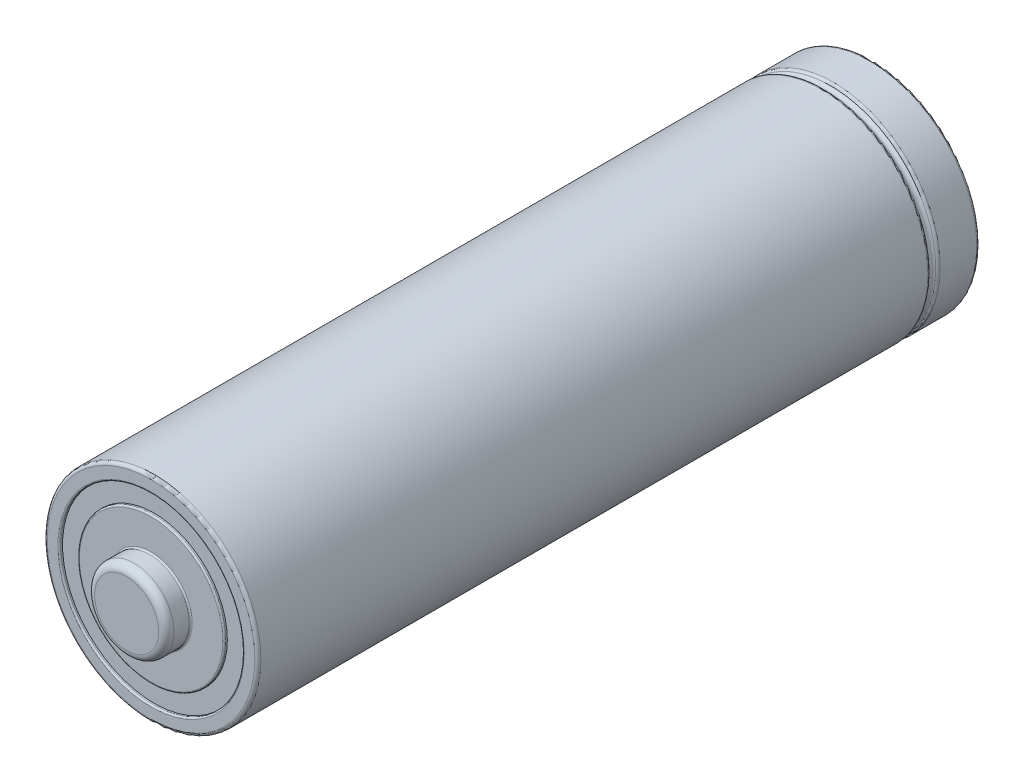
SolidWorks part; units mm, degrees
ref_plane "Płaszczyzna przednia" through (0, 0, 0) normal (0, 0, 1) x (1, 0, 0)
ref_plane "Płaszczyzna górna" through (0, 0, 0) normal (0, 1, 0) x (1, 0, 0)
ref_plane "Płaszczyzna prawa" through (0, 0, 0) normal (1, 0, 0) x (0, 0, -1)
sketch "Szkic1" plane through (0, 0, 0) normal (0, 0, 1) x (1, 0, 0)
  circle A0 centre (0, 0) radius 7
  dimension "D1" = 14
extrude "Dodanie-wyciągnięcie1" add sketch "Szkic1" along normal blind 47.3
sketch "Szkic2" plane through (0, 0, 0) normal (0, 0, -1) x (-1, 0, 0)
  circle A0 centre (0, 0) radius 4.15
  dimension "D1" = 8.3
extrude "Dodanie-wyciągnięcie2" add sketch "Szkic2" along normal blind 0.7
sketch "Szkic3" plane through (0, 0, 47.3) normal (0, 0, 1) x (1, 0, 0)
  circle A0 centre (0, 0) radius 6
  circle A1 centre (0, 0) radius 4.8
  dimension "D1" = 9.6
  dimension "D2" = 12
extrude "Wytnij-wyciągnięcie1" cut sketch "Szkic3" against normal blind 0.2
sketch "Szkic4" plane through (0, 0, 47.3) normal (0, 0, 1) x (1, 0, 0)
  circle A0 centre (0, 0) radius 2.6
  dimension "D1" = 5.2
extrude "Dodanie-wyciągnięcie3" add sketch "Szkic4" along normal blind 1.6
sketch "Szkic5" plane through (0, 0, 0) normal (0, 1, 0) x (1, 0, 0)
  line L0 (7, 0) -> (-7, 0) construction
  line L1 (7, 0) -> (-7, 0) construction
  line L2 (0, 0) -> (0, -6.0016) construction
  line L3 (-7, -2.75) -> (-7, -3.25)
  arc A0 (-7, -3.25) -> (-7, -2.75) centre (-7, -3) ccw
  dimension "D1" = 0.5
  dimension "D2" = 3
revolve "Wycięcie-obrót1" cut sketch "Szkic5" angle 360 about L2
fillet "Zaokrąglenie1" radius 0.7 1 edges at (-4.15, 0, -0.7)
fillet "Zaokrąglenie2" radius 0.2 4 edges at (7, 0, 47.3) (-7, 0, 2.75) (-7, 0, 3.25) (7, 0, 0)
fillet "Zaokrąglenie3" radius 0.5 1 edges at (2.6, 0, 48.9)
fillet "Zaokrąglenie4" radius 0.1 2 edges at (4.8, 0, 47.3) (2.6, 0, 47.3)
fillet "Zaokrąglenie5" radius 0.1 1 edges at (6, 0, 47.3)
fillet "Zaokrąglenie6" radius 0.1 1 edges at (4.15, 0, 0)
